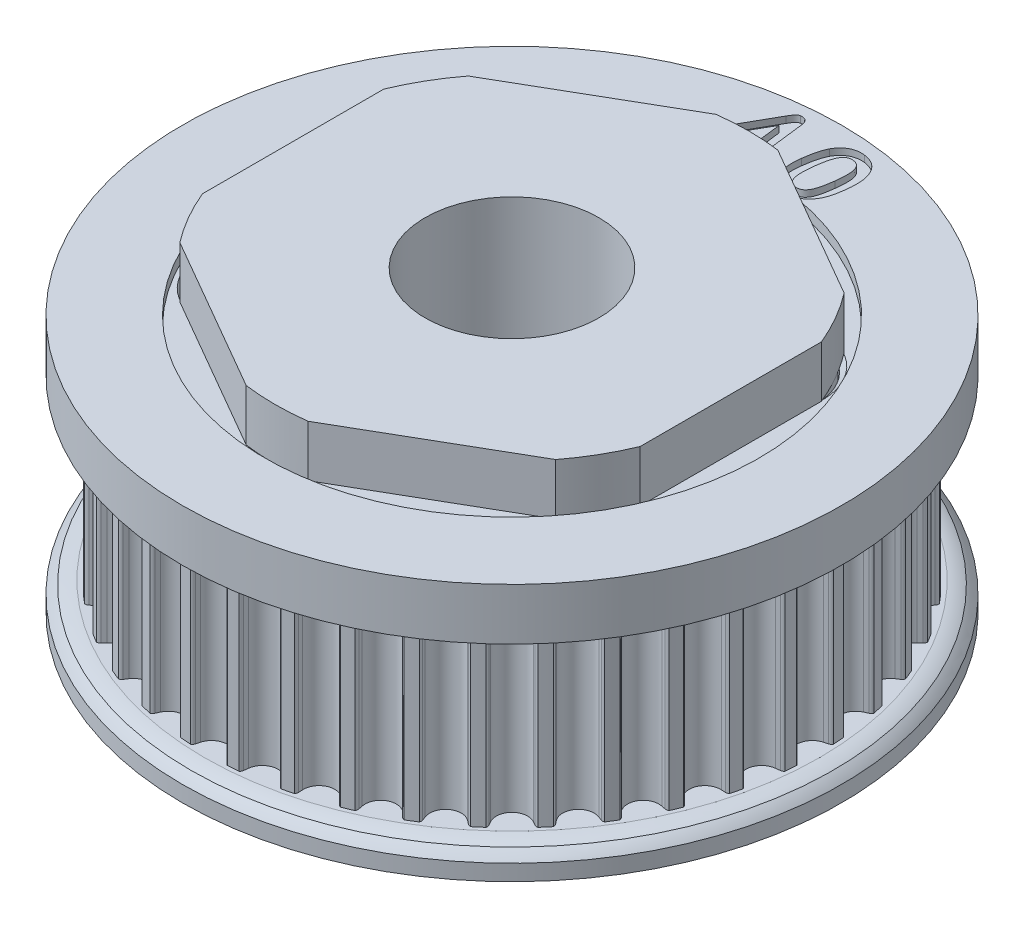
SolidWorks part; units mm, degrees
other "DetailItem2"
material "Markforged"
ref_plane "Front Plane" through (0, 0, 0) normal (0, 0, 1) x (1, 0, 0)
ref_plane "Top Plane" through (0, 0, 0) normal (0, 1, 0) x (1, 0, 0)
ref_plane "Right Plane" through (0, 0, 0) normal (1, 0, 0) x (0, 0, -1)
ref_axis "Centerline" through (0, 11.3983, 0) along (0, -1, 0)
sketch "Sketch1" plane through (0, 0, 0) normal (0, 1, 0) x (1, 0, 0)
  circle A0 centre (0, 0) radius 18.7176
  dimension "OuterDiameter" = 37.4352
extrude "ToothOD" add sketch "Sketch1" along normal mid plane 12.3825
sketch "Sketch2" plane through (0, 0, 0) normal (0, 1, 0) x (1, 0, 0)
  line L0 (0, 17.5492) -> (50000, 17.5492) construction
  line L1 (0, 18.7176) -> (50000, 18.7176) construction
  line L2 (0, 0) -> (0, 50000) construction
  arc A0 (-0.937, 18.2677) -> (0, 17.5492) centre (0, 18.5195) ccw
  arc A1 (-1.1278, 18.6836) -> (1.1278, 18.6836) centre (0, 0) cw
  circle A2 centre (0, 0) radius 18.7176 construction
  arc A3 (-0.937, 18.2677) -> (-1.0078, 18.5195) centre (-11.9754, 15.3012) ccw
  arc A4 (-1.0078, 18.5195) -> (-1.1278, 18.6836) centre (-1.2954, 18.4351) ccw
  circle A5 centre (0, 0) radius 18.7176 construction
  arc A6 (0.937, 18.2677) -> (1.0078, 18.5195) centre (11.9754, 15.3012) cw
  arc A7 (1.0078, 18.5195) -> (1.1278, 18.6836) centre (1.2954, 18.4351) cw
  arc A8 (0, 17.5492) -> (0.937, 18.2677) centre (0, 18.5195) ccw
  dimension "D1" = 1.9406
  dimension "D3" = 22.86
  dimension "D4" = 0.5994
  dimension "D2" = 1.1684
  dimension "D5" = 1.2954
extrude "ToothProfile" cut sketch "Sketch2" against normal through all both and the other way through all
pattern_circular "ToothPattern" count 40 over 360 about axis through (0, 6.1913, 0) along (0, -1, 0) of "ToothProfile"
sketch "Sketch4" plane through (0, 0, 0) normal (0, 0, 1) x (1, 0, 0)
  line L0 (0, -6.1913) -> (18.9716, -6.1913)
  line L1 (0, -7.9375) -> (20.32, -7.9375)
  line L2 (0, -7.9375) -> (0, -6.1913)
  line L3 (20.32, -7.9375) -> (20.32, -6.9532)
  line L4 (0, 0) -> (50000, 0) construction
  line L5 (20.32, 7.9375) -> (20.32, 6.9532)
  line L6 (0, 7.9375) -> (0, 6.1913)
  line L7 (0, 7.9375) -> (20.32, 7.9375)
  line L8 (0, 6.1913) -> (18.9716, 6.1913) construction
  line L9 (0, 6.1913) -> (0, 3.9688)
  line L10 (0, 3.9688) -> (18.9716, 3.9688)
  line L11 (18.9716, 3.9688) -> (20.32, 4.7473)
  line L12 (20.32, 4.7473) -> (20.32, 6.9532)
  line L13 (18.9716, 3.9688) -> (18.9716, 6.1913) construction
  arc A0 (18.9716, -6.1913) -> (19.812, -6.4452) centre (18.6641, -8.7261) cw
  arc A2 (19.812, -6.4452) -> (20.32, -6.9532) centre (17.815, -8.9503) cw
  arc A3 (19.812, 6.4452) -> (20.32, 6.9532) centre (17.815, 8.9503) ccw construction
  arc A4 (18.9716, 6.1913) -> (19.812, 6.4452) centre (18.6641, 8.7261) ccw construction
  dimension "D5" = 2.5534
  dimension "D6" = 3.2036
  dimension "FlangeID" = 18.9716
  dimension "D1" = 1.7463
  dimension "D2" = 0.9843
  dimension "D3" = 6.1913
  dimension "D4" = 15.875
  dimension "D7" = 0.762
  dimension "D8" = 0.508
  dimension "D10" = 0.508
  dimension "D9" = 20.32
  dimension "D11" = 10.16
  dimension "D12" = 30
revolve "Flange" add sketch "Sketch4" angle 360 about axis through (0, 11.3983, 0) along (0, -1, 0)
sketch "Sketch7" plane through (0, 0, 0) normal (0, -1, 0) x (1, 0, 0)
  circle A0 centre (0, 0) radius 5.3581
  dimension "D1" = 10.7163
extrude "Bore" cut sketch "Sketch7" against normal through all both and the other way through all
sketch "Sketch9" plane through (0, 7.9375, 0) normal (0, 1, 0) x (1, 0, 0)
  arc A0 (-10.7763, -10.7763) -> (10.7763, -10.7763) centre (0, 0) cw construction
  text T0 "40" font "Arial Rounded MT Bold" height 4.572
  point P3 (0, 15.24)
  dimension "D1" = 15.24
  dimension "D2" = 270
extrude "Large Tooth Count" cut sketch "Sketch9" against normal blind 0.4 and the other way through all
sketch "Sketch11" plane through (0, 7.9375, 0) normal (0, 1, 0) x (1, 0, 0)
  arc A0 (-4.8314, -4.8314) -> (4.8314, -4.8314) centre (0, 0) cw construction
  text T0 "<b>40</b>" font "Arial Rounded MT Bold" height 2.286
  point P6 (0, 6.8326)
  dimension "D4" = 6.8326
  dimension "D3" = 270
extrude "Small Tooth Count" [suppressed] cut sketch "Sketch11" against normal blind 0.4 and the other way through all
sketch "Sketch14" plane through (0, 0, 0) normal (0, 0, 1) x (1, 0, 0)
  line L0 (20.32, 7.9375) -> (-20.32, 7.9375) construction
  line L1 (0, 7.9375) -> (15.24, 7.9375)
  line L2 (0, 7.9375) -> (0, 7.3025)
  line L3 (0, 7.3025) -> (15.24, 7.3025)
  line L4 (15.24, 7.9375) -> (15.24, 7.3025)
  line L5 (0, 7.9375) -> (15.24, 7.3025) construction
  line L6 (0, 7.3025) -> (15.24, 7.9375) construction
  line L7 (-20.32, -7.9375) -> (20.32, -7.9375) construction
  line L8 (0, -7.9375) -> (15.24, -7.9375)
  line L9 (0, -7.9375) -> (0, -2.2225)
  line L10 (0, -2.2225) -> (15.24, -2.2225)
  line L11 (15.24, -7.9375) -> (15.24, -2.2225)
  line L12 (0, -7.9375) -> (15.24, -2.2225) construction
  line L13 (0, -2.2225) -> (15.24, -7.9375) construction
  line L14 (0, 0) -> (0, 50000) construction
  point P4 (7.62, 7.62)
  point P11 (7.62, -5.08)
  dimension "D1" = 9.525
  dimension "D2" = 15.24
  dimension "D3" = 10.16
revolve "Cut-Revolve1" cut sketch "Sketch14" angle 360 about L14
sketch "Sketch15" plane through (0, -7.9375, 0) normal (0, -1, 0) x (1, 0, 0)
  line L0 (0, 0) -> (0, 11.43) construction
  line L1 (-3.175, 0) -> (-3.175, 11.43)
  line L2 (3.175, 0) -> (3.175, 11.43)
  arc A0 (-3.175, 0) -> (3.175, 0) centre (0, 0) ccw
  arc A1 (3.175, 11.43) -> (-3.175, 11.43) centre (0, 11.43) ccw
  point P3 (0, 5.715)
  dimension "D1" = 3.175
  dimension "D2" = 11.43
extrude "Cut-Extrude1" cut sketch "Sketch15" against normal through all
pattern_circular "CirPattern1" count 6 over 360 about axis through (0, 7.9375, 0) along (0, -1, 0) of "Cut-Extrude1"
fillet "Fillet1" radius 3.175 6 edges at (-6.35, 2.54, 0) (-3.175, 2.54, -5.4993) (3.175, 2.54, -5.4993) (6.35, 2.54, 0) (-3.175, 2.54, 5.4993) (3.175, 2.54, 5.4993)
sketch "Sketch17" plane through (0, -2.2225, 0) normal (0, -1, 0) x (1, 0, 0)
  line L14 (3.175, 10.9985) -> (3.175, 11.43)
  line L16 (8.3112, 8.4646) -> (7.9375, 8.2489)
  line L18 (11.1125, 2.7496) -> (11.4862, 2.9654)
  line L20 (11.4862, -2.9654) -> (11.1125, -2.7496)
  line L22 (7.9375, -8.2489) -> (8.3112, -8.4646)
  line L24 (3.175, -11.43) -> (3.175, -10.9985)
  line L26 (-3.175, -10.9985) -> (-3.175, -11.43)
  line L28 (-8.3112, -8.4646) -> (-7.9375, -8.2489)
  line L30 (-11.1125, -2.7496) -> (-11.4862, -2.9654)
  line L32 (-11.4862, 2.9654) -> (-11.1125, 2.7496)
  line L34 (-7.9375, 8.2489) -> (-8.3112, 8.4646)
  line L37 (-3.175, 11.43) -> (-3.175, 10.9985)
  line L50 (3.175, 10.9985) -> (3.175, 11.43)
  line L51 (8.3112, 8.4646) -> (7.9375, 8.2489)
  line L52 (11.1125, 2.7496) -> (11.4862, 2.9654)
  line L53 (11.4862, -2.9654) -> (11.1125, -2.7496)
  line L54 (7.9375, -8.2489) -> (8.3112, -8.4646)
  line L55 (3.175, -11.43) -> (3.175, -10.9985)
  line L56 (-3.175, -10.9985) -> (-3.175, -11.43)
  line L57 (-8.3112, -8.4646) -> (-7.9375, -8.2489)
  line L58 (-11.1125, -2.7496) -> (-11.4862, -2.9654)
  line L59 (-11.4862, 2.9654) -> (-11.1125, 2.7496)
  line L60 (-7.9375, 8.2489) -> (-8.3112, 8.4646)
  line L61 (-3.175, 11.43) -> (-3.175, 10.9985)
  circle A1 centre (0, 0) radius 5.3581 construction
  circle A8 centre (0, 0) radius 5.3581
  arc A47 (3.175, 10.9985) -> (7.9375, 8.2489) centre (6.35, 10.9985) ccw
  arc A48 (11.4862, 2.9654) -> (8.3112, 8.4646) centre (9.8987, 5.715) ccw
  arc A49 (11.1125, 2.7496) -> (11.1125, -2.7496) centre (12.7, 0) ccw
  arc A50 (8.3112, -8.4646) -> (11.4862, -2.9654) centre (9.8987, -5.715) ccw
  arc A51 (7.9375, -8.2489) -> (3.175, -10.9985) centre (6.35, -10.9985) ccw
  arc A52 (-3.175, -11.43) -> (3.175, -11.43) centre (0, -11.43) ccw
  arc A53 (-3.175, -10.9985) -> (-7.9375, -8.2489) centre (-6.35, -10.9985) ccw
  arc A54 (-11.4862, -2.9654) -> (-8.3112, -8.4646) centre (-9.8987, -5.715) ccw
  arc A55 (-11.1125, -2.7496) -> (-11.1125, 2.7496) centre (-12.7, 0) ccw
  arc A56 (-8.3112, 8.4646) -> (-11.4862, 2.9654) centre (-9.8987, 5.715) ccw
  arc A57 (-7.9375, 8.2489) -> (-3.175, 10.9985) centre (-6.35, 10.9985) ccw
  arc A70 (3.175, 11.43) -> (-3.175, 11.43) centre (0, 11.43) ccw
  arc A71 (3.175, 10.9985) -> (7.9375, 8.2489) centre (6.35, 10.9985) ccw
  arc A72 (11.4862, 2.9654) -> (8.3112, 8.4646) centre (9.8987, 5.715) ccw
  arc A73 (11.1125, 2.7496) -> (11.1125, -2.7496) centre (12.7, 0) ccw
  arc A74 (8.3112, -8.4646) -> (11.4862, -2.9654) centre (9.8987, -5.715) ccw
  arc A75 (7.9375, -8.2489) -> (3.175, -10.9985) centre (6.35, -10.9985) ccw
  arc A76 (-3.175, -11.43) -> (3.175, -11.43) centre (0, -11.43) ccw
  arc A77 (-3.175, -10.9985) -> (-7.9375, -8.2489) centre (-6.35, -10.9985) ccw
  arc A78 (-11.4862, -2.9654) -> (-8.3112, -8.4646) centre (-9.8987, -5.715) ccw
  arc A79 (-11.1125, -2.7496) -> (-11.1125, 2.7496) centre (-12.7, 0) ccw
  arc A80 (-8.3112, 8.4646) -> (-11.4862, 2.9654) centre (-9.8987, 5.715) ccw
  arc A81 (-7.9375, 8.2489) -> (-3.175, 10.9985) centre (-6.35, 10.9985) ccw
  arc A82 (3.175, 11.43) -> (-3.175, 11.43) centre (0, 11.43) ccw
  dimension "D1" = 0
extrude "Boss-Extrude1" add sketch "Sketch17" against normal up to surface (9.525 mm away) separate body up to face at (0, 7.3025, 0)
sketch "Sketch21" plane through (0, -2.2225, 0) normal (0, -1, 0) x (1, 0, 0)
  circle A0 centre (0, 0) radius 7.9375
  dimension "D1" = 15.875
extrude "Cut-Extrude4" cut sketch "Sketch21" against normal blind 2.286
chamfer "Chamfer1" distance 2.54 angle 45 1 edges at (0, -7.9375, -15.24)
chamfer "Chamfer2" distance 0.635 angle 45 1 edges at (0, -2.2225, -15.24)
sketch "Sketch22" plane through (0, 7.3025, 0) normal (0, 1, 0) x (1, 0, 0)
  circle A0 centre (0, 0) radius 5.3581
  circle A1 centre (0, 0) radius 14.605
  arc A2 (8.3112, -8.4646) -> (11.4862, -2.9654) centre (9.8987, -5.715) ccw construction
  circle A3 centre (0, 0) radius 5.3581 construction
extrude "Boss-Extrude2" add sketch "Sketch22" along normal blind 1.5875 separate body
combine bodies "Combine1" operation type add bodies to combine 118 117
sketch "Sketch23" plane through (0, 7.3025, 0) normal (0, 1, 0) x (1, 0, 0)
  line L0 (7.9058, -8.3039) -> (8.2794, -8.5196)
  line L1 (11.5179, -2.9104) -> (11.1442, -2.6946)
  line L2 (11.1442, 2.6946) -> (11.5179, 2.9104)
  line L3 (8.2794, 8.5196) -> (7.9057, 8.3039)
  line L4 (3.2385, 10.9985) -> (3.2385, 11.43)
  line L5 (-3.2385, 11.43) -> (-3.2385, 10.9985)
  line L6 (-7.9058, 8.3039) -> (-8.2794, 8.5196)
  line L7 (-11.5179, 2.9104) -> (-11.1442, 2.6946)
  line L8 (-11.1442, -2.6946) -> (-11.5179, -2.9104)
  line L9 (-8.2794, -8.5196) -> (-7.9057, -8.3039)
  line L10 (-3.2385, -10.9985) -> (-3.2385, -11.43)
  line L11 (3.2385, -11.43) -> (3.2385, -10.9985)
  line L12 (7.9375, -8.2489) -> (8.3112, -8.4646)
  line L13 (3.175, -11.43) -> (3.175, -10.9985)
  line L14 (-3.175, -10.9985) -> (-3.175, -11.43)
  line L15 (-8.3112, -8.4646) -> (-7.9375, -8.2489)
  line L16 (-11.1125, -2.7496) -> (-11.4862, -2.9654)
  line L17 (-11.4862, 2.9654) -> (-11.1125, 2.7496)
  line L18 (-7.9375, 8.2489) -> (-8.3112, 8.4646)
  line L19 (-3.175, 11.43) -> (-3.175, 10.9985)
  line L20 (3.175, 10.9985) -> (3.175, 11.43)
  line L21 (8.3112, 8.4646) -> (7.9375, 8.2489)
  line L22 (11.1125, 2.7496) -> (11.4862, 2.9654)
  line L23 (11.4862, -2.9654) -> (11.1125, -2.7496)
  line L24 (7.9375, -8.2489) -> (8.3112, -8.4646)
  line L25 (3.175, -11.43) -> (3.175, -10.9985)
  line L26 (-3.175, -10.9985) -> (-3.175, -11.43)
  line L27 (-8.3112, -8.4646) -> (-7.9375, -8.2489)
  line L28 (-11.1125, -2.7496) -> (-11.4862, -2.9654)
  line L29 (-11.4862, 2.9654) -> (-11.1125, 2.7496)
  line L30 (-7.9375, 8.2489) -> (-8.3112, 8.4646)
  line L31 (-3.175, 11.43) -> (-3.175, 10.9985)
  line L32 (3.175, 10.9985) -> (3.175, 11.43)
  line L33 (8.3112, 8.4646) -> (7.9375, 8.2489)
  line L34 (11.1125, 2.7496) -> (11.4862, 2.9654)
  line L35 (11.4862, -2.9654) -> (11.1125, -2.7496)
  arc A0 (8.2794, -8.5196) -> (11.5179, -2.9104) centre (9.8987, -5.715) ccw
  arc A1 (11.1442, 2.6946) -> (11.1442, -2.6946) centre (12.7, 0) ccw
  arc A2 (11.5179, 2.9104) -> (8.2794, 8.5196) centre (9.8987, 5.715) ccw
  arc A3 (3.2385, 10.9985) -> (7.9057, 8.3039) centre (6.35, 10.9985) ccw
  arc A4 (3.2385, 11.43) -> (-3.2385, 11.43) centre (0, 11.43) ccw
  arc A5 (-7.9058, 8.3039) -> (-3.2385, 10.9985) centre (-6.35, 10.9985) ccw
  arc A6 (-8.2794, 8.5196) -> (-11.5179, 2.9104) centre (-9.8987, 5.715) ccw
  arc A7 (-11.1442, -2.6946) -> (-11.1442, 2.6946) centre (-12.7, 0) ccw
  arc A8 (-11.5179, -2.9104) -> (-8.2794, -8.5196) centre (-9.8987, -5.715) ccw
  arc A9 (-3.2385, -10.9985) -> (-7.9057, -8.3039) centre (-6.35, -10.9985) ccw
  arc A10 (-3.2385, -11.43) -> (3.2385, -11.43) centre (0, -11.43) ccw
  arc A11 (7.9058, -8.3039) -> (3.2385, -10.9985) centre (6.35, -10.9985) ccw
  arc A12 (7.9375, -8.2489) -> (3.175, -10.9985) centre (6.35, -10.9985) ccw
  arc A13 (-3.175, -11.43) -> (3.175, -11.43) centre (0, -11.43) ccw
  arc A14 (-3.175, -10.9985) -> (-7.9375, -8.2489) centre (-6.35, -10.9985) ccw
  arc A15 (-11.4862, -2.9654) -> (-8.3112, -8.4646) centre (-9.8987, -5.715) ccw
  arc A16 (-11.1125, -2.7496) -> (-11.1125, 2.7496) centre (-12.7, 0) ccw
  arc A17 (-8.3112, 8.4646) -> (-11.4862, 2.9654) centre (-9.8987, 5.715) ccw
  arc A18 (-7.9375, 8.2489) -> (-3.175, 10.9985) centre (-6.35, 10.9985) ccw
  arc A19 (3.175, 11.43) -> (-3.175, 11.43) centre (0, 11.43) ccw
  arc A20 (3.175, 10.9985) -> (7.9375, 8.2489) centre (6.35, 10.9985) ccw
  arc A21 (11.4862, 2.9654) -> (8.3112, 8.4646) centre (9.8987, 5.715) ccw
  arc A22 (11.1125, 2.7496) -> (11.1125, -2.7496) centre (12.7, 0) ccw
  arc A23 (8.3112, -8.4646) -> (11.4862, -2.9654) centre (9.8987, -5.715) ccw
  arc A24 (7.9375, -8.2489) -> (3.175, -10.9985) centre (6.35, -10.9985) ccw
  arc A25 (-3.175, -11.43) -> (3.175, -11.43) centre (0, -11.43) ccw
  arc A26 (-3.175, -10.9985) -> (-7.9375, -8.2489) centre (-6.35, -10.9985) ccw
  arc A27 (-11.4862, -2.9654) -> (-8.3112, -8.4646) centre (-9.8987, -5.715) ccw
  arc A28 (-11.1125, -2.7496) -> (-11.1125, 2.7496) centre (-12.7, 0) ccw
  arc A29 (-8.3112, 8.4646) -> (-11.4862, 2.9654) centre (-9.8987, 5.715) ccw
  arc A30 (-7.9375, 8.2489) -> (-3.175, 10.9985) centre (-6.35, 10.9985) ccw
  arc A31 (3.175, 11.43) -> (-3.175, 11.43) centre (0, 11.43) ccw
  arc A32 (3.175, 10.9985) -> (7.9375, 8.2489) centre (6.35, 10.9985) ccw
  arc A33 (11.4862, 2.9654) -> (8.3112, 8.4646) centre (9.8987, 5.715) ccw
  arc A34 (11.1125, 2.7496) -> (11.1125, -2.7496) centre (12.7, 0) ccw
  arc A35 (8.3112, -8.4646) -> (11.4862, -2.9654) centre (9.8987, -5.715) ccw
  dimension "D1" = 0
  dimension "D2" = 0.0635
extrude "Cut-Extrude5" cut sketch "Sketch23" against normal through all
chamfer "Chamfer3" distance 0.3175 angle 45 54 edges at (-4.7942, 7.3025, 8.3039) (-3.2385, 7.3025, 11.2143) (-8.0926, 7.3025, 8.4118) (0, 7.3025, 14.6685) (-12.7033, 7.3025, 7.3342) (3.2385, 7.3025, 11.2143) (-11.3311, 7.3025, 2.8025) (4.7943, 7.3025, 8.3039) (-9.5885, 7.3025, 0) (8.0926, 7.3025, 8.4118) (-11.3311, 7.3025, -2.8025) (12.7033, 7.3025, 7.3343) (-12.7033, 7.3025, -7.3343) (11.3311, 7.3025, 2.8025) (-8.0926, 7.3025, -8.4118) (9.5885, 7.3025, 0) (-4.7943, 7.3025, -8.3039) (11.3311, 7.3025, -2.8025) (-3.2385, 7.3025, -11.2143) (12.7033, 7.3025, -7.3342) (0, 7.3025, -14.6685) (8.0926, 7.3025, -8.4118) (3.2385, 7.3025, -11.2143) (4.7942, 7.3025, -8.3039) (-10.3811, -2.2225, 8.9174) (-2.5321, -2.2225, 13.449) (-8.0926, -2.2225, 8.4118) (-3.2385, -2.2225, 11.2143) (-4.7942, -2.2225, 8.3039) (2.5321, -2.2225, 13.449) (10.3811, -2.2225, 8.9174) (3.2385, -2.2225, 11.2143) (8.0926, -2.2225, 8.4118) (4.7943, -2.2225, 8.3039) (12.9132, -2.2225, 4.5316) (12.9132, -2.2225, -4.5316) (11.3311, -2.2225, 2.8025) (11.3311, -2.2225, -2.8025) (9.5885, -2.2225, 0) (10.3811, -2.2225, -8.9174) (2.5321, -2.2225, -13.449) (8.0926, -2.2225, -8.4118) (3.2385, -2.2225, -11.2143) (4.7942, -2.2225, -8.3039) (-2.5321, -2.2225, -13.449) (-10.3811, -2.2225, -8.9174) (-3.2385, -2.2225, -11.2143) (-8.0926, -2.2225, -8.4118) (-4.7943, -2.2225, -8.3039) (-12.9132, -2.2225, -4.5316) (-12.9132, -2.2225, 4.5316) (-11.3311, -2.2225, -2.8025) (-11.3311, -2.2225, 2.8025) (-9.5885, -2.2225, 0)
sketch "Sketch24" plane through (0, 8.89, 0) normal (0, 1, 0) x (1, 0, 0)
  line L1 (0, 15.5812) -> (-13.4938, 7.7906)
  line L2 (-13.4938, 7.7906) -> (-13.4938, -7.7906)
  line L3 (-13.4938, -7.7906) -> (0, -15.5812)
  line L4 (0, -15.5812) -> (13.4937, -7.7906)
  line L5 (13.4937, -7.7906) -> (13.4938, 7.7906)
  line L6 (13.4938, 7.7906) -> (0, 15.5812)
  circle A0 centre (0, 0) radius 13.4938 construction
  circle A1 centre (0, 0) radius 20.32
  circle A3 centre (0, 0) radius 20.32 construction
  dimension "D1" = 26.9875
extrude "Cut-Extrude6" cut sketch "Sketch24" against normal through all
delete or keep bodies "Body-Delete/Keep 1" [suppressed] bodies 119
delete or keep bodies "Body-Delete/Keep 2" [suppressed] type keep bodies bodies 120
delete or keep bodies "Body-Delete/Keep 3" [suppressed] type keep bodies bodies 118
sketch "Sketch25" plane through (0, 8.89, 0) normal (0, 1, 0) x (1, 0, 0)
  line L6 (11.5861, 8.892) -> (1.9076, 14.4799)
  line L7 (-1.9076, 14.4799) -> (-11.5861, 8.892)
  line L8 (-13.4938, 5.5879) -> (-13.4938, -5.5879)
  line L9 (-11.5861, -8.892) -> (-1.9076, -14.4799)
  line L10 (1.9076, -14.4799) -> (11.5861, -8.892)
  line L11 (13.4937, -5.5879) -> (13.4938, 5.5879)
  line L12 (11.5861, 8.892) -> (1.9076, 14.4799)
  line L13 (-1.9076, 14.4799) -> (-11.5861, 8.892)
  line L14 (-13.4938, 5.5879) -> (-13.4938, -5.5879)
  line L15 (-11.5861, -8.892) -> (-1.9076, -14.4799)
  line L16 (1.9076, -14.4799) -> (11.5861, -8.892)
  line L17 (13.4937, -5.5879) -> (13.4938, 5.5879)
  circle A0 centre (0, 0) radius 5.3581 construction
  circle A1 centre (0, 0) radius 5.3581
  arc A6 (13.4938, 5.5879) -> (11.5861, 8.892) centre (0, 0) ccw
  arc A7 (1.9076, 14.4799) -> (-1.9076, 14.4799) centre (0, 0) ccw
  arc A8 (-11.5861, 8.892) -> (-13.4938, 5.5879) centre (0, 0) ccw
  arc A9 (-13.4938, -5.5879) -> (-11.5861, -8.892) centre (0, 0) ccw
  arc A10 (-1.9076, -14.4799) -> (1.9076, -14.4799) centre (0, 0) ccw
  arc A11 (11.5861, -8.892) -> (13.4937, -5.5879) centre (0, 0) ccw
  arc A12 (13.4938, 5.5879) -> (11.5861, 8.892) centre (0, 0) ccw
  arc A13 (1.9076, 14.4799) -> (-1.9076, 14.4799) centre (0, 0) ccw
  arc A14 (-11.5861, 8.892) -> (-13.4938, 5.5879) centre (0, 0) ccw
  arc A15 (-13.4938, -5.5879) -> (-11.5861, -8.892) centre (0, 0) ccw
  arc A16 (-1.9076, -14.4799) -> (1.9076, -14.4799) centre (0, 0) ccw
  arc A17 (11.5861, -8.892) -> (13.4937, -5.5879) centre (0, 0) ccw
  dimension "D1" = 0
extrude "Boss-Extrude3" add sketch "Sketch25" along normal offset from surface (1.5875 mm away) 12.7 up to face at (0, -2.2225, -7.9375)
equation "\"OuterDiameter@Sketch1\"= \"OD\""
equation "\"Teeth\"= \"No_Teeth\""
equation "\"PD\"= \"No_Teeth\" * 3mm / pi"
equation "\"OD\"= \"PD\" - .030"
equation "\"ToothCount@ToothPattern\" = \"Teeth\""
equation "\"Angle\"= 360 / \"Teeth\""
equation "\"AngleSpacing@ToothPattern\" = \"Angle\""
equation "\"FlangeID@Sketch4\"=\"OD\"/2+.01"
equation "\"D3@Sketch4\"=\"Tooth_Face_Length\"/2"
equation "\"Bearing_Feature\"= \"Bearing_Boss\""
equation "\"TopBearingBoss\" = IIF ( \"Bearing_Feature\" > 0 , \"unsuppressed\" , \"suppressed\" )"
equation "\"HexBore\"= \"Hex_Bore\" + \"Print_Tolerance\""
equation "\"Large Tooth Count\" = iif ( \"No_Teeth\" < \"TextTooth\" , \"suppressed\" , \"unsuppressed\" )"
equation "\"Small Tooth Count\"= iif ( \"No_Teeth\" < \"TextTooth\" , \"unsuppressed\" , \"suppressed\" )"
equation "\"BottomBearingBoss\" = iif ( \"Bearing_Feature\" > 1 , \"unsuppressed\" , \"suppressed\" )"
equation "\"ToothFaceLength@ToothOD\" = \"Tooth_Face_Length\""
equation "\"D4@Sketch4\" = \"Width_No_BearingBoss\""
equation "\"TextTooth\"= iif ( \"Hex_Bore\" <= .380 , 23 , iif ( \"Hex_Bore\" <= .505 , 25 , 16 ) )"
equation "\"D4@Sketch11\"=\"HexBore\"/2+.08"
